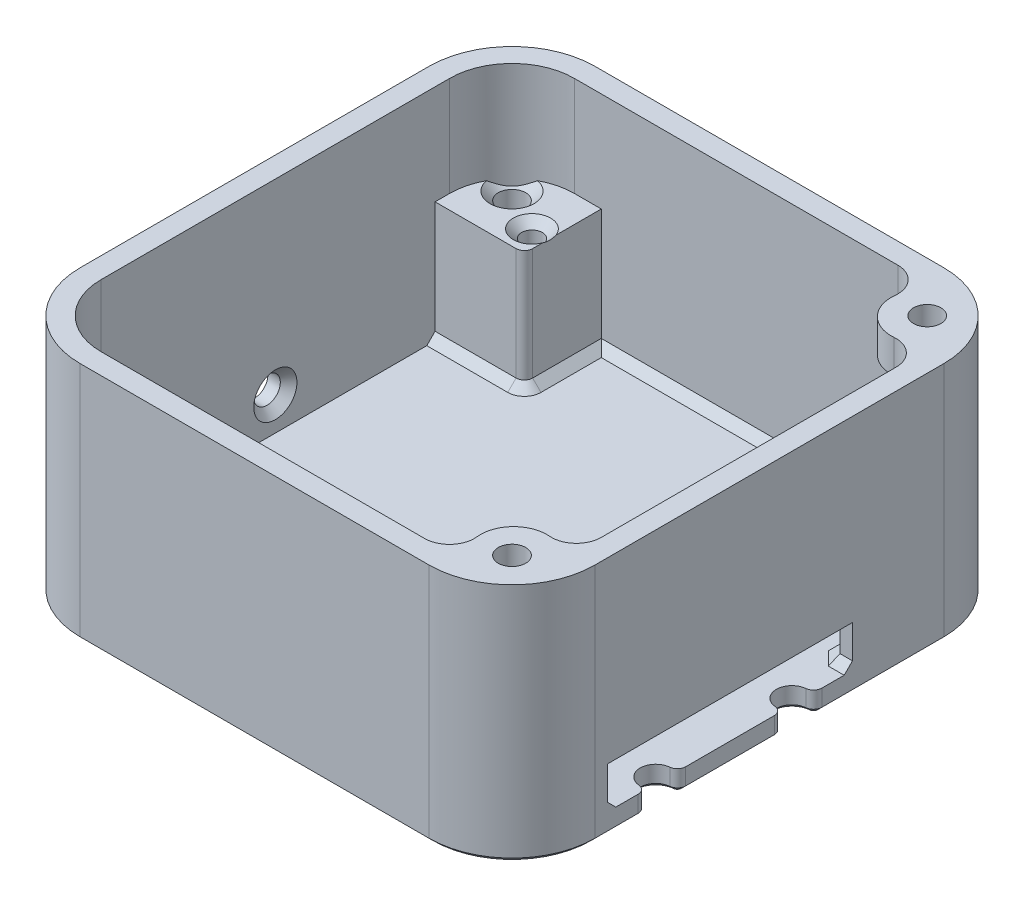
SolidWorks part; units mm, degrees
material "ABS"
ref_plane "Alzado" through (0, 0, 0) normal (0, 0, 1) x (1, 0, 0)
ref_plane "Planta" through (0, 0, 0) normal (0, 1, 0) x (1, 0, 0)
ref_plane "Vista lateral" through (0, 0, 0) normal (1, 0, 0) x (0, 0, -1)
sketch "Croquis1" plane through (0, 0, 0) normal (0, 1, 0) x (1, 0, 0)
  line L0 (0, 31) -> (62, 31)
  line L1 (62, -31) -> (0, -31)
  line L2 (62, 31) -> (62, -31)
  line L3 (0, 31) -> (0, -31)
  point P4 (0, 0)
  dimension "D1" = 62
  dimension "D2" = 62
extrude "Saliente-Extruir1" add sketch "Croquis1" along normal blind 29
fillet "Redondeo1" radius 10 2 edges at (62, 14.5, -31) (62, 14.5, 31)
fillet "Redondeo2" radius 10 2 edges at (0, 14.5, 31) (0, 14.5, -31)
shell "Vaciado1" thickness 2.5 removed face at (31, 29, 0) removed face at (31, 0, 0)
sketch "Croquis4" plane through (0, 0, 0) normal (0, -1, 0) x (1, 0, 0)
  line L0 (2.5, -21) -> (2.5, 21) construction
  line L1 (7.5, 28.5) -> (54.5, 28.5)
  line L2 (2.5, 23.5) -> (2.5, -23.5)
  line L3 (7.5, -28.5) -> (54.5, -28.5)
  line L4 (59.5, 23.5) -> (59.5, -23.5)
  line L5 (59.5, 21) -> (59.5, -21) construction
  line L6 (10, 28.5) -> (52, 28.5) construction
  line L7 (52, -28.5) -> (10, -28.5) construction
  arc A2 (54.5, -28.5) -> (59.5, -23.5) centre (54.5, -23.5) ccw
  arc A3 (54.5, 28.5) -> (59.5, 23.5) centre (54.5, 23.5) cw
  arc A4 (2.5, -23.5) -> (7.5, -28.5) centre (7.5, -23.5) ccw
  arc A5 (7.5, 28.5) -> (2.5, 23.5) centre (7.5, 23.5) ccw
  dimension "D1" = 5
  dimension "D2" = 5
extrude "Saliente-Extruir2" add sketch "Croquis4" against normal blind 2.5
sketch "Croquis6" plane through (62, 0, 0) normal (1, 0, 0) x (0, 0, -1)
  line L0 (-21, 0) -> (21, 0) construction
  line L1 (-19.5, 7.5) -> (10, 7.5)
  line L2 (-19.5, 7.5) -> (-19.5, 2.5)
  line L3 (-19.5, 2.5) -> (10, 2.5)
  line L4 (10, 7.5) -> (10, 2.5)
  line L5 (-31, 0) -> (-31, 29) construction
  dimension "D1" = 2.5
  dimension "D2" = 29.5
  dimension "D3" = 5
  dimension "D4" = 11.5
extrude "Cortar-Extruir4" cut sketch "Croquis6" against normal blind 10
sketch "Croquis7" plane through (0, 0, 0) normal (-1, 0, 0) x (0, 0, 1)
  circle A0 centre (0, 6.5) radius 1.6
  dimension "D1" = 3.2
  dimension "D2" = 6.5
extrude "Cortar-Extruir5" cut sketch "Croquis7" against normal blind 10
sketch "Croquis8" plane through (0, 2.5, 0) normal (0, 1, 0) x (1, 0, 0)
  line L0 (-10.3165, 0) -> (70.8731, 0) construction
  line L1 (7.5, 28.5) -> (13.25, 28.5)
  line L2 (2.5, 23.5) -> (2.5, 19.2385)
  line L3 (2.5, 19.2385) -> (13.25, 19.2385)
  line L4 (13.25, 28.5) -> (13.25, 19.2385)
  line L5 (54.5, 28.5) -> (53.5, 28.5)
  line L6 (59.5, 23.5) -> (59.5, 19.5)
  line L7 (59.5, 19.5) -> (53.5, 19.5)
  line L8 (53.5, 28.5) -> (53.5, 19.5)
  line L9 (53.5, -28.5) -> (53.5, -19.5)
  line L10 (59.5, -19.5) -> (53.5, -19.5)
  line L11 (59.5, -23.5) -> (59.5, -19.5)
  line L12 (54.5, -28.5) -> (53.5, -28.5)
  line L13 (13.25, -28.5) -> (13.25, -19.2385)
  line L14 (2.5, -19.2385) -> (13.25, -19.2385)
  line L15 (2.5, -23.5) -> (2.5, -19.2385)
  line L16 (7.5, -28.5) -> (13.25, -28.5)
  line L17 (10, -28.5) -> (52, -28.5) construction
  line L18 (59.5, -21) -> (59.5, 21) construction
  line L19 (2.5, 21) -> (2.5, -21) construction
  line L20 (52, 28.5) -> (10, 28.5) construction
  arc A0 (59.5, -23.5) -> (54.5, -28.5) centre (54.5, -23.5) cw
  arc A1 (54.5, 28.5) -> (59.5, 23.5) centre (54.5, 23.5) cw
  arc A2 (7.5, 28.5) -> (2.5, 23.5) centre (7.5, 23.5) ccw
  arc A3 (2.5, -23.5) -> (7.5, -28.5) centre (7.5, -23.5) ccw
  point P26 (59.5, -28.5)
  point P29 (59.5, 28.5)
  point P34 (2.5, 28.5)
  point P37 (2.5, -28.5)
  dimension "D1" = 5
  dimension "D5" = 5
  dimension "D2" = 10.75
  dimension "D3" = 6
  dimension "D4" = 9
extrude "Saliente-Extruir3" add sketch "Croquis8" along normal blind 14.5
sketch "Croquis9" plane through (0, 17, 0) normal (0, 1, 0) x (1, 0, 0)
  line L1 (11.1508, 22.25) -> (55.6508, 22.25) construction
  line L2 (11.1508, 22.25) -> (11.1508, -22.25) construction
  line L3 (11.1508, -22.25) -> (55.6508, -22.25) construction
  line L4 (55.6508, 22.25) -> (55.6508, -22.25) construction
  circle A0 centre (11.1508, 22.25) radius 1.25
  circle A1 centre (11.1508, -22.25) radius 1.25
  circle A2 centre (55.6508, -22.25) radius 1.25
  circle A3 centre (55.6508, 22.25) radius 1.25
  point P9 (11.1508, 0)
  dimension "D1" = 2.5
  dimension "D2" = 44.5
  dimension "D3" = 44.5
extrude "Cortar-Extruir6" cut sketch "Croquis9" against normal blind 14
fillet "Redondeo3" radius 1 4 edges at (53.5, 9.75, 19.5) (13.25, 9.75, 19.2385) (13.25, 9.75, -19.2385) (53.5, 9.75, -19.5)
sketch "Croquis10" plane through (0, 29, 0) normal (0, 1, 0) x (1, 0, 0)
  line L0 (21.1012, 0) -> (70.4759, 0) construction
  circle A0 centre (55.9275, 24.7249) radius 4
  circle A1 centre (55.9275, -24.7249) radius 4
  dimension "D1" = 8
extrude "Saliente-Extruir4" add sketch "Croquis10" against normal blind 4
fillet "Redondeo4" radius 3 4 edges at (59.3245, 27, 22.6129) (53.9983, 27, 28.2289) (59.3245, 27, -22.6129) (53.9983, 27, -28.2289)
sketch "Croquis11" plane through (0, 29, 0) normal (0, 1, 0) x (1, 0, 0)
  line L0 (52, 31) -> (10, 31) construction
  line L1 (6, 25) -> (56, 25) construction
  line L2 (6, 25) -> (6, -25) construction
  line L3 (6, -25) -> (56, -25) construction
  line L4 (56, 25) -> (56, -25) construction
  line L5 (0, 21) -> (0, -21) construction
  circle A0 centre (6, 25) radius 1.65
  circle A1 centre (6, -25) radius 1.65
  circle A2 centre (56, -25) radius 1.65
  circle A3 centre (56, 25) radius 1.65
  point P5 (6, 0)
  dimension "D1" = 3.3
  dimension "D2" = 50
  dimension "D3" = 6
  dimension "D4" = 6
extrude "Cortar-Extruir7" cut sketch "Croquis11" against normal blind 11
sketch "Croquis12" plane through (0, 17, 0) normal (0, 1, 0) x (1, 0, 0)
  line L0 (52, 31) -> (10, 31) construction
  line L1 (0, 21) -> (0, -21) construction
  line L2 (-15.35, 0) -> (20.7527, 0) construction
  circle A0 centre (6, 25) radius 1.65
  circle A1 centre (6, -25) radius 1.65
  dimension "D1" = 3.3
  dimension "D2" = 6
  dimension "D3" = 6
extrude "Cortar-Extruir8" cut sketch "Croquis12" against normal through all
chamfer "Chaflán1" distance 1 angle 45 2 edges at (6, 17, 26.65) (6, 17, -23.35)
chamfer "Chaflán2" distance 1 angle 45 4 edges at (55.6508, 17, 23.5) (11.1508, 17, 23.5) (55.6508, 17, -21) (11.1508, 17, -21)
chamfer "Chaflán3" distance 1 angle 45 2 edges at (59.5, 7.5, 4.75) (59.5, 5, -10)
sketch "Croquis13" plane through (0, 0, 0) normal (0, -1, 0) x (1, 0, 0)
  line L1 (6.1851, 20.4129) -> (10.0651, 22.8668)
  line L2 (10.0651, 22.8668) -> (9.88, 27.4539)
  line L3 (9.88, 27.4539) -> (5.8149, 29.5871)
  line L4 (5.8149, 29.5871) -> (1.9349, 27.1332)
  line L5 (1.9349, 27.1332) -> (2.12, 22.5461)
  line L6 (2.12, 22.5461) -> (6.1851, 20.4129)
  line L7 (10.5432, -24.3405) -> (7.7004, -20.7357)
  line L8 (7.7004, -20.7357) -> (3.1572, -21.3952)
  line L9 (3.1572, -21.3952) -> (1.4568, -25.6595)
  line L10 (1.4568, -25.6595) -> (4.2996, -29.2643)
  line L11 (4.2996, -29.2643) -> (8.8428, -28.6048)
  line L12 (8.8428, -28.6048) -> (10.5432, -24.3405)
  circle A0 centre (6, 25) radius 3.9758 construction
  circle A1 centre (6, -25) radius 3.9758 construction
  dimension "D1" = 7.9516
sketch "Croquis14" plane through (0, 0, 0) normal (0, -1, 0) x (1, 0, 0)
  line L0 (52.9619, 4.75) -> (70.4211, 4.75) construction
  line L1 (62, 19.5) -> (62, -10) construction
  circle A0 centre (61.2618, 12.95) radius 1.875
  circle A1 centre (61.2618, -3.45) radius 1.875
  point P8 (62, 4.75)
  dimension "D1" = 3.75
  dimension "D2" = 8.2
extrude "Cortar-Extruir10" cut sketch "Croquis14" against normal blind 4
fillet "Redondeo6" radius 1 4 edges at (62, 1.25, -1.7264) (62, 1.25, -5.1736) (62, 1.25, 14.6736) (62, 1.25, 11.2264)
chamfer "Chaflán4" distance 1 angle 45 1 edges at (2.5, 6.5, -1.6)
chamfer "Chaflán5" distance 1 angle 45 19 edges at (59.5, 2.5, -15.25) (57, 2.5, -19.5) (53.7929, 2.5, -19.7929) (53.5, 2.5, -24.4242) (58.25, 2.5, 19.5) (53.7929, 2.5, 19.7929) (53.5, 2.5, 24.4242) (52.7538, 2.5, 28.462) (32.625, 2.5, 28.5) (13.25, 2.5, 24.3693) (12.9571, 2.5, 19.5314) (7.375, 2.5, 19.2385) (7.375, 2.5, -19.2385) (52.7538, 2.5, -28.462) (12.9571, 2.5, -19.5314) (32.625, 2.5, -28.5) (13.25, 2.5, -24.3693) (61.25, 2.5, -10) (60, 2.5, -10.5)
chamfer "Chaflán6" distance 0.5 angle 45 16 edges at (62, 0, 4.75) (61.7386, 0, -1.2611) (61.7386, 0, 10.7611) (59.3868, 0, -3.45) (59.3868, 0, 12.95) (61.7386, 0, -5.6389) (61.7386, 0, 15.1389) (62, 0, -13.6565) (62, 0, 18.4065) (59.0711, 0, -28.0711) (59.0711, 0, 28.0711) (31, 0, -31) (31, 0, 31) (2.9289, 0, -28.0711) (2.9289, 0, 28.0711) (0, 0, 0)
